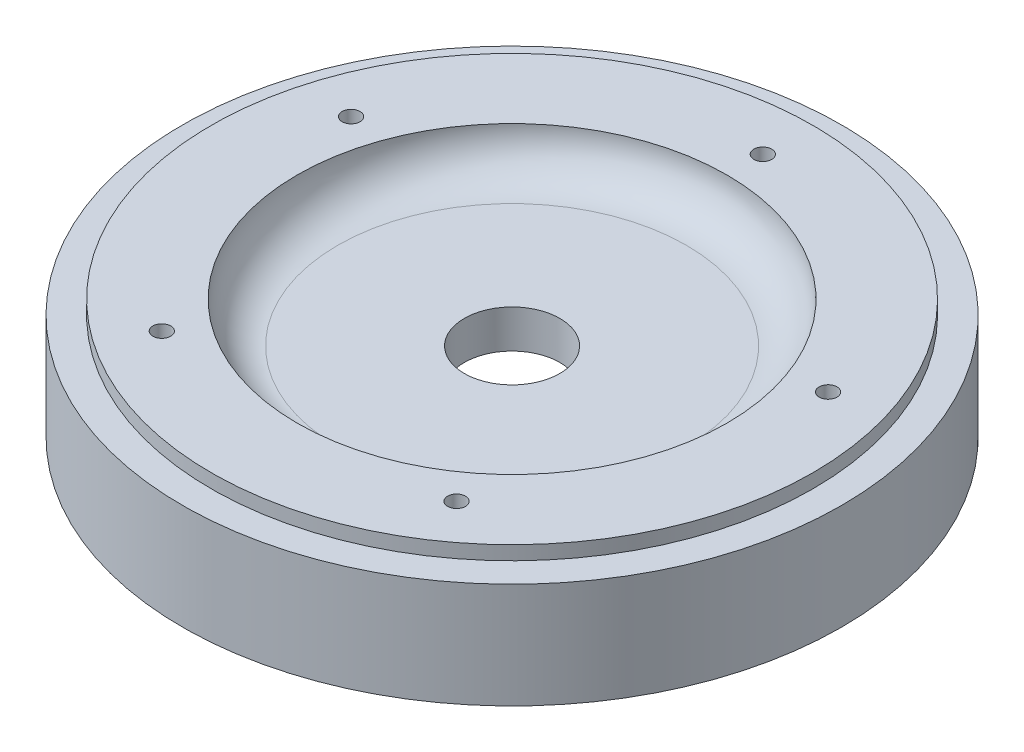
SolidWorks part; units mm, degrees
ref_plane "Front Plane" through (0, 0, 0) normal (0, 0, 1) x (1, 0, 0)
ref_plane "Top Plane" through (0, 0, 0) normal (0, 1, 0) x (1, 0, 0)
ref_plane "Right Plane" through (0, 0, 0) normal (1, 0, 0) x (0, 0, -1)
sketch "Sketch1" plane through (0, 0, 0) normal (0, 0, 1) x (1, 0, 0)
  line L0 (87.63, 0) -> (57.15, 0)
  line L1 (57.15, 0) -> (57.15, 10.795)
  line L2 (57.15, 10.795) -> (0, 10.795)
  line L3 (0, 10.795) -> (0, 20.955)
  line L4 (0, 20.955) -> (57.15, 20.955)
  line L5 (57.15, 20.955) -> (57.15, 31.75)
  line L6 (57.15, 31.75) -> (79.9973, 31.75)
  line L7 (79.9973, 31.75) -> (79.9973, 28.0416)
  line L8 (79.9973, 28.0416) -> (87.63, 28.0416)
  line L9 (87.63, 28.0416) -> (87.63, 0)
  point P10 (0, 15.875)
  dimension "D1" = 10.16
  dimension "D2" = 87.63
  dimension "D3" = 57.15
  dimension "D4" = 57.15
  dimension "D5" = 31.75
  dimension "D6" = 3.7084
  dimension "D7" = 79.9973
  dimension "D8" = 20.955
revolve "Revolve1" add sketch "Sketch1" angle 360 about L3
hole_wizard "1 (1) Diameter Hole1" positions "Sketch2" profile "Sketch4" hole size "1" standard "ANSI Inch" end condition through all
sketch "Sketch2" plane through (0, 20.955, 0) normal (0, 1, 0) x (1, 0, 0)
  point P0 (0, 0)
sketch "Sketch4" plane through (0, 20.955, 0) normal (1, 0, 0) x (0, 0, 1)
  line L0 (0, 0) -> (0, 20.955)
  line L1 (0, 20.955) -> (12.7, 20.955)
  line L2 (12.7, 20.955) -> (12.7, 0)
  line L5 (12.7, 0) -> (0, 0)
  line L11 (0, -6.35) -> (0, 107.95) construction
  dimension "Thru Hole Dia." = 25.4
  dimension "Thru Hole Depth" = 20.955
hole_wizard "3/16 (0.187) Dowel Hole1" positions "Sketch5" profile "Sketch7" hole size "3/16" standard "ANSI Inch"
sketch "Sketch5" plane through (0, 31.75, 0) normal (0, 1, 0) x (1, 0, 0)
  point P0 (0, 66.675)
  dimension "D1" = 66.675
sketch "Sketch7" plane through (0, 31.75, -66.675) normal (1, 0, 0) x (0, 0, 1)
  line L0 (0, 0) -> (0, 11.079)
  line L1 (0, 11.079) -> (2.3749, 9.652)
  line L2 (2.3749, 9.652) -> (2.3749, 0)
  line L5 (2.3749, 0) -> (0, 0)
  line L10 (0, 11.079) -> (-2.3749, 9.652) construction
  line L11 (0, -6.35) -> (0, 107.95) construction
  dimension "Hole Dia." = 4.7498
  dimension "Hole Depth" = 9.652
  dimension "Drill Angle" = 118
pattern_circular "CirPattern1" count 5 over 360 about axis through (0, 31.75, 0) along (0, -1, 0) of "3/16 (0.187) Dowel Hole1"
fillet "Fillet2" radius 10.795 2 edges at (57.15, 10.795, 0) (57.15, 20.955, 0)
